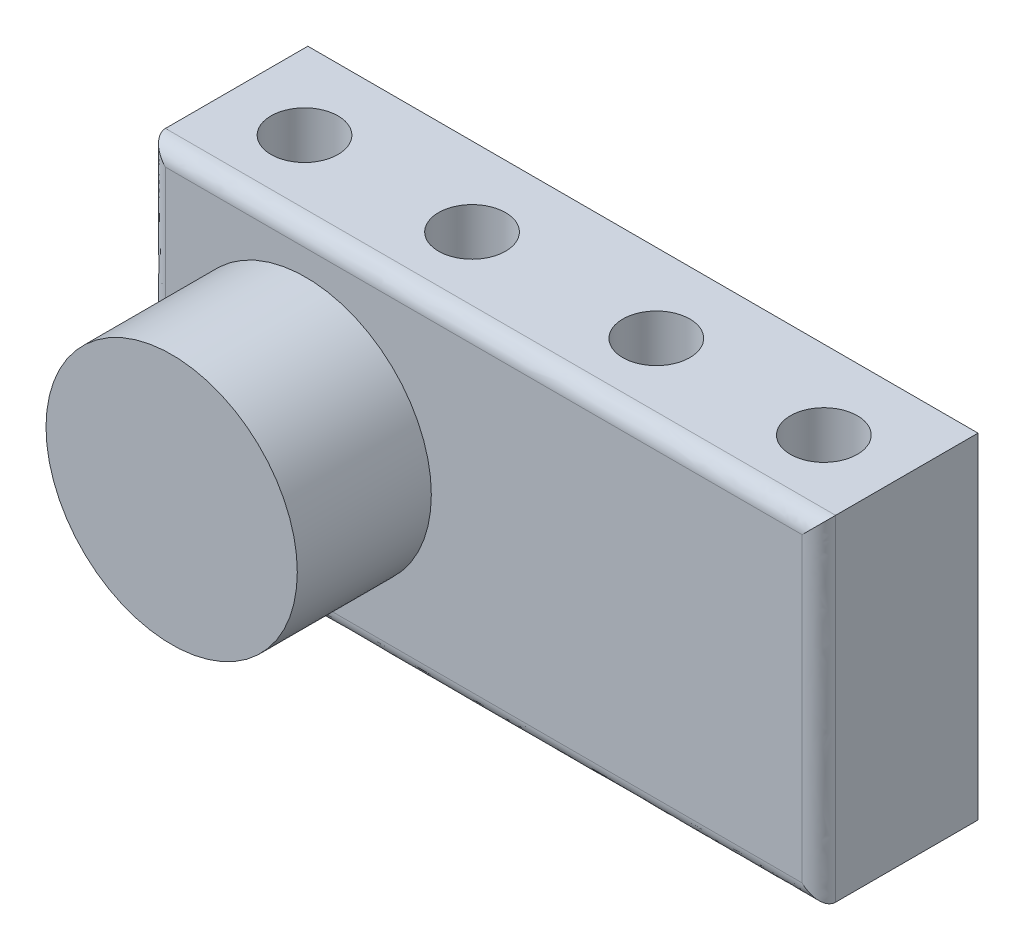
SolidWorks part; units mm, degrees
material "petg 20%"
ref_plane "Front Plane" through (0, 0, 0) normal (0, 0, 1) x (1, 0, 0)
ref_plane "Top Plane" through (0, 0, 0) normal (0, 1, 0) x (1, 0, 0)
ref_plane "Right Plane" through (0, 0, 0) normal (1, 0, 0) x (0, 0, -1)
sketch "Sketch1" plane through (0, 0, 0) normal (0, 0, 1) x (1, 0, 0)
  line L1 (-20, 10) -> (20, 10)
  line L2 (-20, 10) -> (-20, -10)
  line L3 (-20, -10) -> (20, -10)
  line L4 (20, 10) -> (20, -10)
  line L5 (-20, 10) -> (20, -10) construction
  line L6 (-20, -10) -> (20, 10) construction
  point P0 (0, 0)
  dimension "D1" = 40
  dimension "D2" = 20
extrude "Boss-Extrude1" add sketch "Sketch1" along normal blind 9.5
fillet "Fillet1" radius 1 4 edges at (0, -10, 9.5) (20, 0, 9.5) (0, 10, 9.5) (-20, 0, 9.5) first distance on face at (0, -10, 4.75) first distance on face at (20, 0, 4.75) first distance on face at (0, 10, 4.75) first distance on face at (-20, 0, 4.75)
sketch "Sketch4" plane through (0, 0, 9.5) normal (0, 0, 1) x (1, 0, 0)
  circle A0 centre (-10.6286, 0) radius 7.5
  dimension "D1" = 15
extrude "Boss-Extrude2" add sketch "Sketch4" along normal blind 8
sketch "Sketch5" plane through (0, -10, 0) normal (0, -1, 0) x (1, 0, 0)
  circle A0 centre (-15.5, 4.7) radius 2
  circle A1 centre (-5.5, 4.7) radius 2
  circle A2 centre (5.5, 4.7) radius 2
  circle A3 centre (15.5, 4.7) radius 2
extrude "Cut-Extrude1" cut sketch "Sketch5" against normal through all
